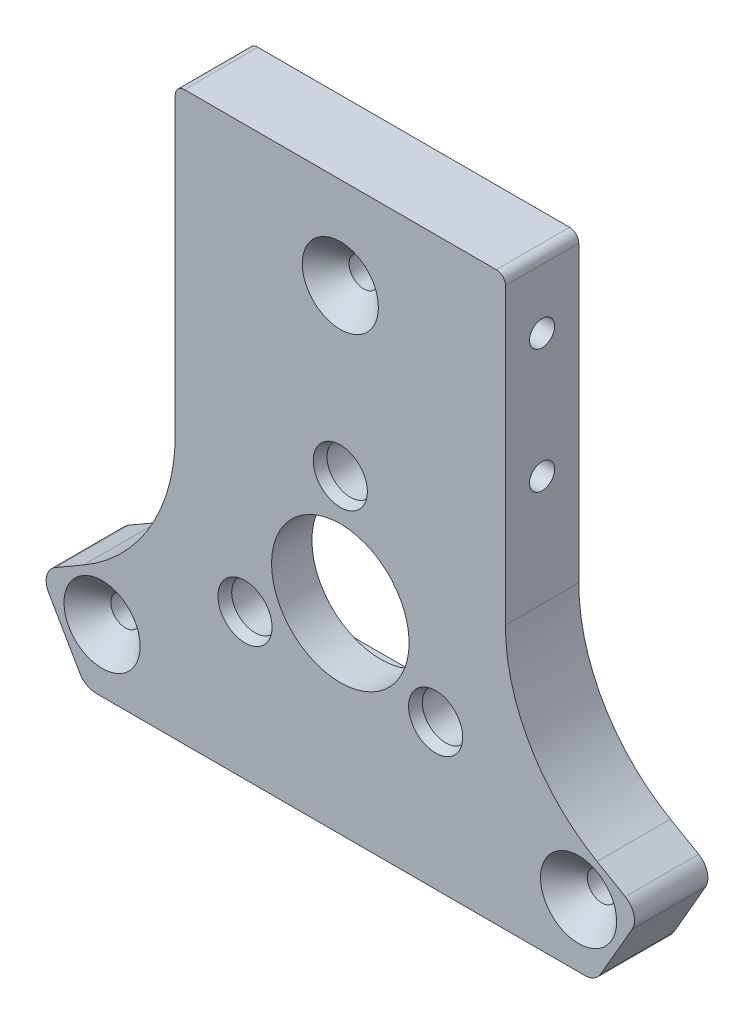
SolidWorks part; units mm, degrees
note: '?' marks a value the reader was unsure of.
other "tool plate" parameters "D3"=8, "D5"=17.4451, "D1"=15.1752, "D2"=4.8248, "D4"=5.0211
ref_plane "Front" through (0, 0, 0) normal (0, 0, 1) x (1, 0, 0)
ref_plane "Top" through (0, 0, 0) normal (0, 1, 0) x (1, 0, 0)
ref_plane "Right" through (0, 0, 0) normal (1, 0, 0) x (0, 0, -1)
sketch "Sketch1" plane through (0, 0, 0) normal (0, 0, 1) x (1, 0, 0)
  line L0 (0, 0) -> (0, 30) construction
  line L1 (0, 0) -> (-25.9808, -15) construction
  line L2 (0, 0) -> (25.9808, -15) construction
  line L4 (-6, -1) -> (6, -1)
  line L5 (-6, -1) -> (-6, 1)
  line L6 (-6, 1) -> (6, 1)
  line L7 (6, -1) -> (6, 1)
  line L8 (-6, -1) -> (6, 1) construction
  line L9 (-6, 1) -> (6, -1) construction
  circle A0 centre (0, 0) radius 2.5
  circle A1 centre (0, 30) radius 4
  circle A2 centre (25.9808, -15) radius 4
  circle A3 centre (-25.9808, -15) radius 4
  dimension "D4" = 5
  dimension "D7" = 8
  dimension "D1" = 30
  dimension "D2" = 120
  dimension "D3" = 120
  dimension "D5" = 12
  dimension "D6" = 2
ref_plane "Plane1" through (0, 30, 0) normal (0, 1, 0) x (1, 0, 0)
sketch "Sketch2" plane through (0, 0, 0) normal (0, 0, 1) x (1, 0, 0)
  line L0 (0, 0) -> (0, 30) construction
  line L1 (0, 0) -> (0, 30) construction
  line L2 (-18, 40) -> (18, 40)
  line L3 (18, 40) -> (18, -4.6188)
  line L4 (-18, 40) -> (-18, -4.6188)
  line L5 (18, -4.6188) -> (32.8109, -13.1699)
  line L6 (32.8109, -13.1699) -> (27.8109, -21.8301)
  line L7 (27.8109, -21.8301) -> (-27.8109, -21.8301)
  line L8 (0, 0) -> (25.9808, -15) construction
  line L9 (30.3109, -17.5) -> (25.9808, -15) construction
  line L10 (-32.8109, -13.1699) -> (-27.8109, -21.8301)
  line L11 (-18, -4.6188) -> (-32.8109, -13.1699)
  circle A0 centre (25.9808, -15) radius 4 construction
  circle A1 centre (0, 0) radius 7.5
  point P8 (0, 40)
  point P19 (0, -21.8301)
  dimension "D5" = 15
  dimension "D1" = 18
  dimension "D2" = 10
  dimension "D3" = 5
  dimension "D4" = 10
extrude "Boss-Extrude1" add sketch "Sketch2" along normal blind 8
hole_wizard "CSK for M3 Flat Head Machine Screw2" positions "Sketch8" profile "Sketch9" countersink size "M3" standard "ANSI Metric"
sketch "Sketch8" plane through (0, 0, 8) normal (0, 0, 1) x (1, 0, 0)
  point P0 (-25.9808, -15)
  point P3 (0, 30)
  point P6 (25.9808, -15)
sketch "Sketch9" plane through (-25.9808, -15, 8) normal (1, 0, 0) x (0, -1, 0)
  line L0 (0, 0) -> (0, 8.9604)
  line L1 (0, 8.9604) -> (1.6, 7.999)
  line L2 (1.6, 7.999) -> (1.6, 2.55)
  line L3 (1.6, 2.55) -> (4.15, 0)
  line L5 (4.15, 0) -> (0, 0)
  line L6 (-1.6, 2.55) -> (-4.15, 0) construction
  line L10 (0, 8.9604) -> (-1.6, 7.999) construction
  line L11 (0, -6.35) -> (0, 107.95) construction
  dimension "Hole Dia." = 3.2
  dimension "Hole Depth" = 7.999
  dimension "Near C'Sink Dia." = 8.3
  dimension "Near C'Sink Angle" = 90
  dimension "Drill Angle" = 118
fillet "Fillet1" radius 20 2 edges at (-18, -4.6188, 4) (18, -4.6188, 4)
sketch "Sketch44" plane through (0, 0, 0) normal (0, 0, -1) x (-1, 0, 0)
  line L0 (10.3923, 10) -> (-10.3923, 10)
  line L1 (0, -20) -> (17.3205, 10) construction
  line L2 (17.3205, 10) -> (-17.3205, 10) construction
  line L3 (-17.3205, 10) -> (0, -20) construction
  line L4 (-13.8564, 4) -> (-3.4641, -14)
  line L5 (3.4641, -14) -> (13.8564, 4)
  line L6 (-17.3205, 10) -> (0, -20) construction
  line L7 (0, -20) -> (17.3205, 10) construction
  line L8 (17.3205, 10) -> (-17.3205, 10) construction
  circle A0 centre (0, 0) radius 10 construction
  arc A1 (-3.4641, -14) -> (3.4641, -14) centre (0, -12) ccw
  arc A2 (10.3923, 10) -> (13.8564, 4) centre (10.3923, 6) cw
  arc A3 (-10.3923, 10) -> (-13.8564, 4) centre (-10.3923, 6) ccw
  dimension "D1" = 20
  dimension "D3" = 4
  dimension "D2" = 0
extrude "v-groove cutout" [suppressed] cut sketch "Sketch44" against normal blind 3.6
sketch "Sketch13" [suppressed] plane through (0, 0, 0) normal (0, 0, -1) x (-1, 0, 0)
  circle A0 centre (-10.3923, 6) radius 2.55
  circle A1 centre (10.3923, 6) radius 2.55
  circle A2 centre (0, -12) radius 2.55
  arc A3 (-10.3923, 10) -> (-13.8564, 4) centre (-10.3923, 6) ccw construction
  arc A4 (13.8564, 4) -> (10.3923, 10) centre (10.3923, 6) ccw construction
  arc A5 (-3.4641, -14) -> (3.4641, -14) centre (0, -12) ccw construction
  dimension "D1" = 5.1
extrude "standard tapered insert cutout" [suppressed] cut sketch "Sketch13" against normal through all and the other way through all
chamfer "taper for inserts" [suppressed] distance 0.4 angle 70
other "Move Face1" [suppressed] parameters "D1"=0.5
sketch "Sketch47" plane through (0, 0, 0) normal (0, 0, -1) x (-1, 0, 0)
  line L1 (-3.4641, 14) -> (-13.8564, -4)
  line L2 (-10.3923, -10) -> (10.3923, -10)
  line L3 (13.8564, -4) -> (3.4641, 14)
  circle A0 centre (0, 0) radius 10 construction
  arc A1 (10.3923, -10) -> (13.8564, -4) centre (10.3923, -6) ccw
  arc A2 (-13.8564, -4) -> (-10.3923, -10) centre (-10.3923, -6) ccw
  arc A3 (-3.4641, 14) -> (3.4641, 14) centre (0, 12) cw
  dimension "D1" = 20
  dimension "D2" = 4
extrude "v-groove cutout flipped" cut sketch "Sketch47" against normal blind 3.6
sketch "Sketch49" plane through (0, 0, 3.6) normal (0, 0, -1) x (-1, 0, 0)
  circle A0 centre (0, 12) radius 2.55
  circle A1 centre (10.3923, -6) radius 2.55
  circle A2 centre (-10.3923, -6) radius 2.55
  dimension "D1" = 5.1
extrude "Cut-Extrude3" cut sketch "Sketch49" against normal through all
chamfer "Chamfer2" distance 0.4 angle 70 3 edges at (7.8423, -6, 8) (-12.9423, -6, 8) (-2.55, 12, 8) first distance on face at (-2.55, 12, 8)
other "Move Face2" flip direction yes face at (-12.9904, -7.5, 1.8) face at (0, -10, 1.8) face at (12.9904, -7.5, 1.8) face at (8.6603, 5, 1.8) face at (0, 15, 1.8) face at (-8.6603, 5, 1.8) parameters "D1"=0.5
ref_axis "Axis2" through (0, 30, 0) along (0, 0, 1)?
sketch "Sketch46" plane through (0, 30, 0) normal (0, 1, 0) x (1, 0, 0)
  line L0 (0, 0) -> (0, 0.3) construction
  line L1 (0, 4.3) -> (0, -3.7)
  circle A0 centre (0, 0.3) radius 4 construction
  arc A1 (0, -3.7) -> (0, 4.3) centre (0, 0.3) cw
  dimension "D1" = 8
  dimension "D2" = 0.3
revolve "tool ball cutout" cut sketch "Sketch46" angle 360 about L0
pattern_circular "CirPattern2" count 3 over 360 about axis through (0, 0, 0) along (0, 0, 1) of "tool ball cutout"
sketch "Sketch20" plane through (18, 0, 0) normal (1, 0, 0) x (0, 0, -1)
  line L0 (-4, 32.5) -> (-4, 40) construction
  line L1 (-8, 40) -> (0, 40) construction
  line L2 (-4, 32.5) -> (-4, 19) construction
  circle A0 centre (-4, 19) radius 1.375
  circle A1 centre (-4, 32.5) radius 1.375
  dimension "D1" = 2.75
  dimension "D2" = 7.5
  dimension "D3" = 13.5
extrude "Tool Wing Screw Holes" cut sketch "Sketch20" against normal blind 4
mirror "Mirror2" about plane through (0, 0, 0) normal (1, 0, 0) of "Tool Wing Screw Holes"
ref_plane "Plane6" through (0, -5.8301, 0) normal (0, -1, 0) x (-1, 0, 0)
fillet "Fillet17" radius 2 4 edges at (27.8109, -21.8301, 4) (32.8109, -13.1699, 4) (-27.8109, -21.8301, 4) (-32.8109, -13.1699, 4)
ref_plane "Plane7" through (0, -15.8301, 0) normal (0, -1, 0) x (-1, 0, 0)
fillet "Fillet18" radius 1 2 edges at (-18, 40, 4) (18, 40, 4)
sketch "Sketch50" plane through (0, -21.8301, 0) normal (0, -1, 0) x (1, 0, 0)
  line L0 (-15, 4) -> (15, 4) construction
  line L1 (-26.6562, 8) -> (26.6562, 8) construction
  circle A0 centre (-15, 4) radius 1.375
  circle A1 centre (15, 4) radius 1.375
  point P2 (0, 4)
  dimension "D3" = 2.75
  dimension "D1" = 4
  dimension "D2" = 30
extrude "Cut-Extrude4" cut sketch "Sketch50" against normal blind 4 contours A0 | A1
equation "\"base_tool_plate_width\"= 36"
equation "\"D1@Sketch2\"=\"base_tool_plate_width\"/2"
